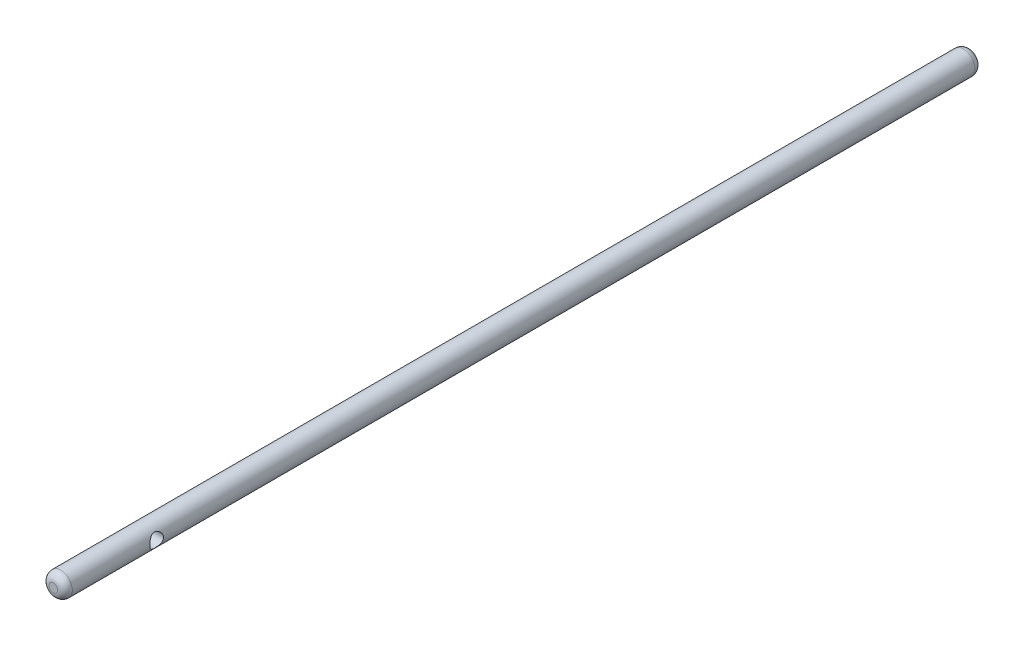
SolidWorks part; units mm, degrees
ref_plane "Front Plane" through (0, 0, 0) normal (0, 0, 1) x (1, 0, 0)
ref_plane "Top Plane" through (0, 0, 0) normal (0, 1, 0) x (1, 0, 0)
ref_plane "Right Plane" through (0, 0, 0) normal (1, 0, 0) x (0, 0, -1)
sketch "Sketch1" plane through (0, 0, 0) normal (0, 0, 1) x (1, 0, 0)
  circle A0 centre (0, 0) radius 12.7
  point P0 (0, 0)
  dimension "D1" = 25.4
extrude "Boss-Extrude1" add sketch "Sketch1" along normal blind 500 and the other way blind 500
sketch "Sketch3" plane through (0, 0, 0) normal (1, 0, 0) x (0, 0, -1)
  line L0 (-500, 12.7) -> (-500, -12.7) construction
  line L1 (500, 12.7) -> (-500, 12.7) construction
  circle A0 centre (-400, 0.2) radius 7.5
  dimension "D1" = 15
  dimension "D2" = 100
  dimension "D3" = 12.5
fillet "Fillet1" radius 8 2 edges at (12.7, 0, 500) (12.7, 0, -500)
extrude "Cut-Extrude1" cut sketch "Sketch3" against normal blind 19 and the other way blind 15 contours A0
